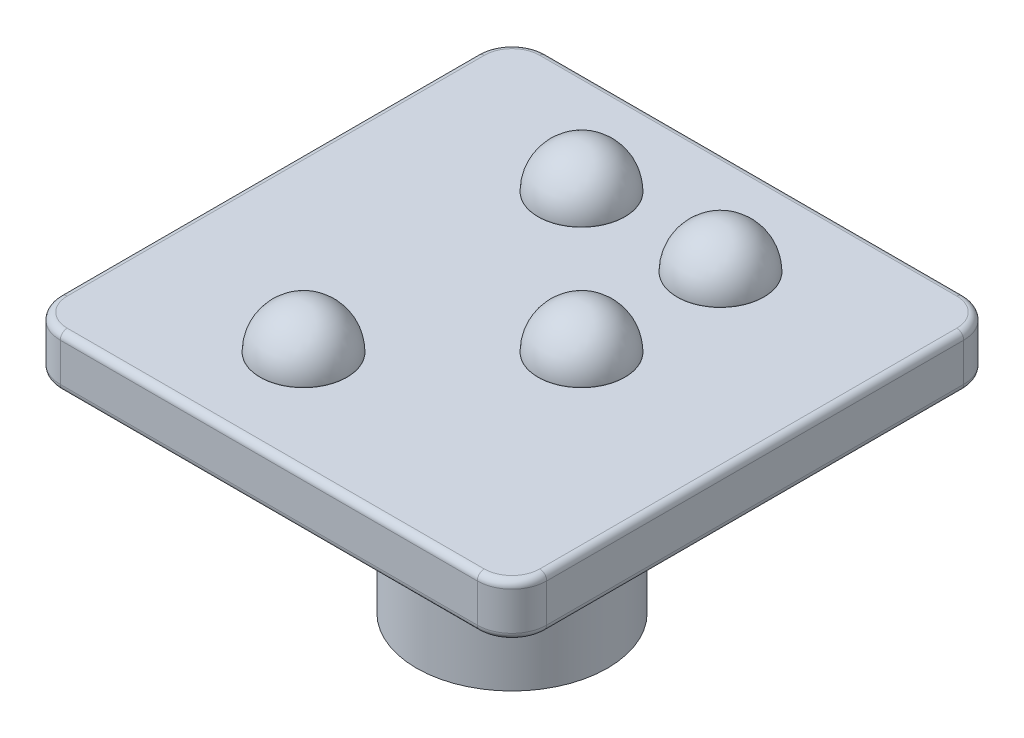
SolidWorks part; units mm, degrees
ref_plane "Front Plane" through (0, 0, 0) normal (0, 0, 1) x (1, 0, 0)
ref_plane "Top Plane" through (0, 0, 0) normal (0, 1, 0) x (1, 0, 0)
ref_plane "Right Plane" through (0, 0, 0) normal (1, 0, 0) x (0, 0, -1)
sketch "Sketch1" plane through (0, 0, 0) normal (0, 1, 0) x (1, 0, 0)
  line L1 (-7.3247, 4.3967) -> (4.6753, 4.3967)
  line L2 (-8.3247, 3.3967) -> (-8.3247, -8.6033)
  line L3 (-7.3247, -9.6033) -> (4.6753, -9.6033)
  line L4 (5.6753, 3.3967) -> (5.6753, -8.6033)
  arc A0 (-8.3247, -8.6033) -> (-7.3247, -9.6033) centre (-7.3247, -8.6033) ccw
  arc A1 (4.6753, -9.6033) -> (5.6753, -8.6033) centre (4.6753, -8.6033) ccw
  arc A2 (4.6753, 4.3967) -> (5.6753, 3.3967) centre (4.6753, 3.3967) cw
  arc A3 (-7.3247, 4.3967) -> (-8.3247, 3.3967) centre (-7.3247, 3.3967) ccw
  point P8 (5.6753, -9.6033)
  point P11 (5.6753, 4.3967)
  point P14 (-8.3247, 4.3967)
  dimension "D3" = 1
  dimension "D1" = 14
  dimension "D2" = 14
extrude "Boss-Extrude1" add sketch "Sketch1" along normal blind 1.5
sketch "Sketch2" plane through (0, 0, 0) normal (0, -1, 0) x (1, 0, 0)
  line L0 (-7.3247, 9.6033) -> (4.6753, 9.6033) construction
  line L1 (5.6753, 8.6033) -> (5.6753, -3.3967) construction
  line L2 (-1.3247, -4.3967) -> (-1.3247, 9.6033) construction
  line L3 (-8.3247, 2.6033) -> (5.6753, 2.6033) construction
  line L4 (-8.3247, -3.3967) -> (-8.3247, 8.6033) construction
  circle A0 centre (-1.3247, 2.6033) radius 2.75
  dimension "D1" = 7
  dimension "D2" = 7
extrude "Boss-Extrude2" add sketch "Sketch2" along normal blind 6
sketch "Sketch3" plane through (0, -6, 0) normal (0, -1, 0) x (1, 0, 0)
  line L0 (-1.3247, 5.3533) -> (-1.3247, -0.1467) construction
  line L1 (-3.3247, 3.1533) -> (0.6753, 3.1533)
  line L2 (-3.3247, 3.1533) -> (-3.3247, 2.0533)
  line L3 (-3.3247, 2.0533) -> (0.6753, 2.0533)
  line L4 (0.6753, 3.1533) -> (0.6753, 2.0533)
  line L5 (-1.8747, 4.6033) -> (-0.7747, 4.6033)
  line L6 (-1.8747, 4.6033) -> (-1.8747, 0.6033)
  line L7 (-1.8747, 0.6033) -> (-0.7747, 0.6033)
  line L8 (-0.7747, 4.6033) -> (-0.7747, 0.6033)
  line L9 (-4.0747, 2.6033) -> (1.4253, 2.6033) construction
  circle A3 centre (-1.3247, 2.6033) radius 2.75 construction
  circle A4 centre (-1.3247, 2.6033) radius 2.75 construction
  dimension "D7" = 0.55
  dimension "D1" = 4
  dimension "D2" = 1.1
  dimension "D3" = 1.1
  dimension "D4" = 4
  dimension "D8" = 0.55
extrude "Cut-Extrude1" cut sketch "Sketch3" against normal blind 6 contours L8 L5 L6 L1 | L1 L8 L3 L4 | L8 L1 L6 L3 | L6 L1 L2 L3 | L8 L3 L6 L7 region at (-2.5997, -6, 2.6033) region at (-1.3247, -6, 3.8783) region at (-1.3247, -6, 2.6033) region at (-0.0497, -6, 2.6033) region at (-1.3247, -6, 1.3283)
chamfer "Chamfer1" distance 0.3 angle 45 12 edges at (-1.3247, -6, 0.6033) (-1.8747, -6, 1.3283) (-2.5997, -6, 2.0533) (-3.3247, -6, 2.6033) (-2.5997, -6, 3.1533) (-0.7747, -6, 1.3283) (-0.0497, -6, 2.0533) (0.6753, -6, 2.6033) (-0.0497, -6, 3.1533) (-0.7747, -6, 3.8783) (-1.3247, -6, 4.6033) (-1.8747, -6, 3.8783)
fillet "Fillet1" radius 1 1 edges at (-1.3247, 0, -0.1467)
sketch "Sketch4" plane through (0, 1.5, 0) normal (0, 1, 0) x (1, 0, 0)
  line L0 (-1.3247, 4.3967) -> (-1.3247, -9.6033) construction
  line L1 (4.6753, 4.3967) -> (-7.3247, 4.3967) construction
  line L2 (-7.3247, -9.6033) -> (4.6753, -9.6033) construction
  line L3 (5.6753, -2.6033) -> (-8.3247, -2.6033) construction
  line L4 (-8.3247, 3.3967) -> (-8.3247, -8.6033) construction
  line L5 (5.6753, -8.6033) -> (5.6753, 3.3967) construction
  line L6 (-3.3247, 4.3967) -> (-3.3247, -9.6033) construction
  line L7 (0.6753, 4.3967) -> (0.6753, -9.6033) construction
  line L8 (-8.3247, 1.3967) -> (5.6753, 1.3967) construction
  line L9 (5.6753, -6.6033) -> (-8.3247, -6.6033) construction
  circle A0 centre (-3.3247, 1.3967) radius 1.25
  circle A1 centre (0.6753, -2.6033) radius 1.25
  circle A3 centre (-3.3247, -6.6033) radius 1.25
  circle A5 centre (0.6753, 1.3967) radius 1.25
  dimension "D1" = 4
  dimension "D2" = 4
  dimension "D3" = 2
  dimension "D4" = 2
extrude "Boss-Extrude3" add sketch "Sketch4" along normal blind 0.01
dome "Dome1" faces to dome 1 distance 1.25 reverse direction no elliptical dome no face at (-3.3247, 1.51, -0.1467) parameters "D1"=1.25
dome "Dome2" faces to dome 1 distance 1.25 reverse direction no elliptical dome no face at (0.6753, 1.51, -0.1467) parameters "D1"=1.25
dome "Dome4" faces to dome 1 distance 1.25 reverse direction no elliptical dome no face at (0.6753, 1.51, 3.8533) parameters "D1"=1.25
dome "Dome5" faces to dome 1 distance 1.25 reverse direction no elliptical dome no face at (-3.3247, 1.51, 7.8533) parameters "D1"=1.25
fillet "Fillet3" radius 0.2 16 edges at (5.3824, 1.5, -4.1038) (5.6753, 1.5, 2.6033) (5.3824, 1.5, 9.3104) (-1.3247, 1.5, 9.6033) (-8.0318, 1.5, 9.3104) (-8.0318, 1.5, -4.1038) (-8.3247, 1.5, 2.6033) (-1.3247, 1.5, -4.3967) (5.3824, 0, 9.3104) (5.6753, 0, 2.6033) (5.3824, 0, -4.1038) (-1.3247, 0, -4.3967) (-8.0318, 0, -4.1038) (-8.3247, 0, 2.6033) (-8.0318, 0, 9.3104) (-1.3247, 0, 9.6033)
